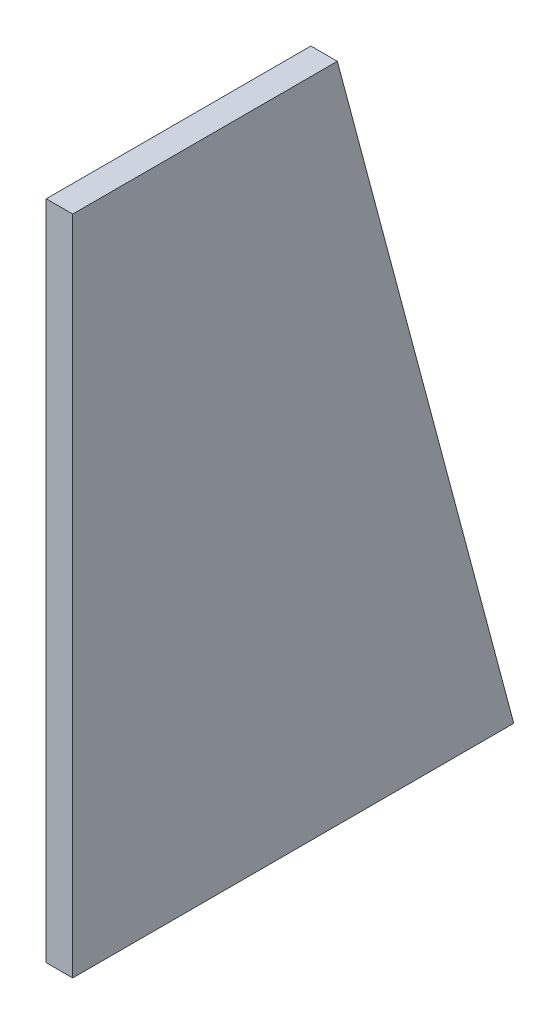
SolidWorks part; units mm, degrees
ref_plane "Спереди" through (0, 0, 0) normal (0, 0, 1) x (1, 0, 0)
ref_plane "Сверху" through (0, 0, 0) normal (0, 1, 0) x (1, 0, 0)
ref_plane "Справа" through (0, 0, 0) normal (1, 0, 0) x (0, 0, -1)
sketch "Эскиз1" plane through (0, 0, 0) normal (1, 0, 0) x (0, 0, -1)
  line L0 (0, 0) -> (100, 0)
  line L1 (0, 0) -> (0, 150)
  line L2 (0, 150) -> (60, 150)
  line L3 (60, 150) -> (100, 0)
extrude "Бобышка-Вытянуть1" add sketch "Эскиз1" along normal blind 6
sketch "Эскиз2" plane through (0, 0, 0) normal (0, -1, 0) x (1, 0, 0)
  point P11 (3, -50)
